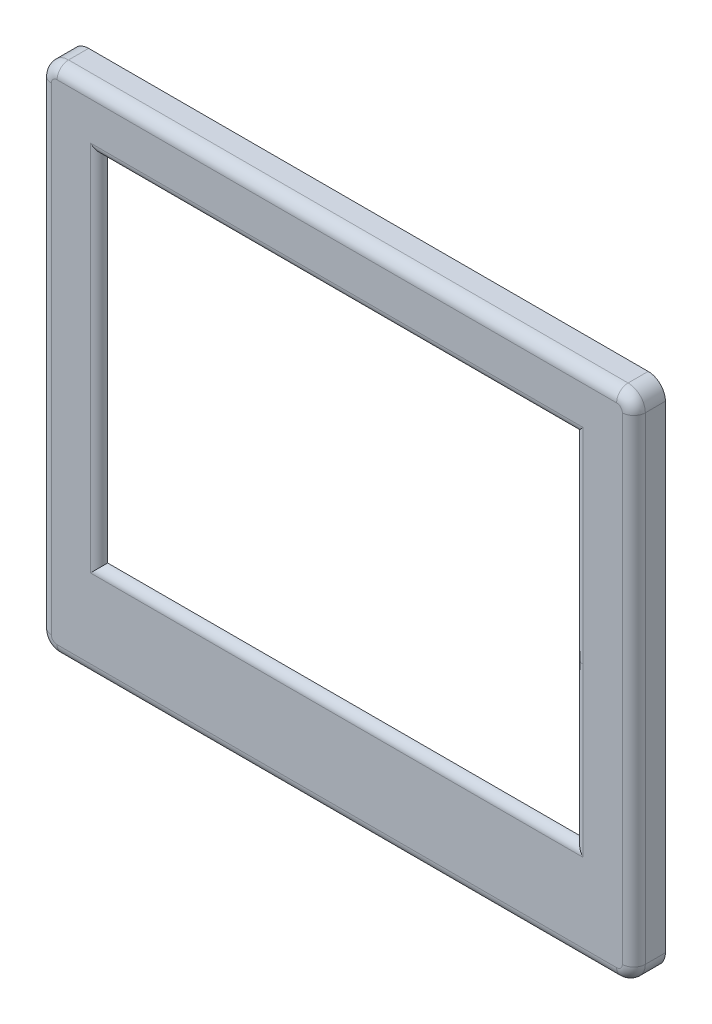
SolidWorks part; units mm, degrees
ref_plane "前视基准面" through (0, 0, 0) normal (0, 0, 1) x (1, 0, 0)
ref_plane "上视基准面" through (0, 0, 0) normal (0, 1, 0) x (1, 0, 0)
ref_plane "右视基准面" through (0, 0, 0) normal (1, 0, 0) x (0, 0, -1)
other "Configuration Table"
sketch "草图1" plane through (0, 0, 0) normal (0, 0, 1) x (1, 0, 0)
  line L0 (0, 0) -> (0, 44.3828) construction
  line L1 (-45.75, 38.75) -> (45.75, 38.75)
  line L2 (-45.75, 38.75) -> (-45.75, -38.75)
  line L3 (-45.75, -38.75) -> (45.75, -38.75)
  line L4 (45.75, 38.75) -> (45.75, -38.75)
  line L5 (-45.75, 38.75) -> (45.75, -38.75) construction
  line L6 (-45.75, -38.75) -> (45.75, 38.75) construction
  line L7 (-42.95, 35.75) -> (42.95, 35.75)
  line L8 (-42.95, 35.75) -> (-42.95, -29.15)
  line L9 (-42.95, -29.15) -> (42.95, -29.15)
  line L10 (42.95, 35.75) -> (42.95, -29.15)
  line L11 (-48.7681, 44.3828) -> (48.7681, 44.3828)
  line L12 (-51.7681, 41.3828) -> (-51.7681, -41.8828)
  line L13 (-48.7681, -44.8828) -> (48.7681, -44.8828)
  line L14 (51.7681, 41.3828) -> (51.7681, -41.8828)
  line L15 (0, 0) -> (-45.75, 0) construction
  line L16 (-8.75, -38.75) -> (-8.75, -41.25)
  line L17 (-8.75, -41.25) -> (8.75, -41.25)
  line L18 (8.75, -41.25) -> (8.75, -38.75)
  circle A0 centre (-48.2681, 40.8828) radius 1.65
  circle A1 centre (-48.2681, -40.8828) radius 1.65
  circle A2 centre (48.2681, -40.8828) radius 1.65
  circle A3 centre (48.2681, 40.8828) radius 1.65
  arc A4 (-51.7681, -41.8828) -> (-48.7681, -44.8828) centre (-48.7681, -41.8828) ccw
  arc A5 (51.7681, -41.8828) -> (48.7681, -44.8828) centre (48.7681, -41.8828) cw
  arc A6 (51.7681, 41.3828) -> (48.7681, 44.3828) centre (48.7681, 41.3828) ccw
  arc A7 (-48.7681, 44.3828) -> (-51.7681, 41.3828) centre (-48.7681, 41.3828) ccw
  point P0 (0, 0)
  point P6 (0, 0)
  dimension "D7" = 3.3
  dimension "D12" = 3.3
  dimension "D14" = 3
  dimension "D1" = 91.5
  dimension "D2" = 77.5
  dimension "D3" = 3
  dimension "D4" = 2.8
  dimension "D5" = 2.8
  dimension "D6" = 9.6
  dimension "D8" = 3.3
  dimension "D9" = 3.5
  dimension "D10" = 3.5
  dimension "D11" = 3.3
  dimension "D13" = 4
  dimension "D15" = 37
  dimension "D16" = 37
  dimension "D17" = 2.5
extrude "凸台-拉伸1" add sketch "草图1" against normal blind 4 contours L11 A7 L12 A4 L13 A5 L14 A6 A3 L1 L4 L3 L2 A0 A1 A2 region at (0, 43.0158, 0)
extrude "凸台-拉伸2" add sketch "草图1<3>" along normal blind 1.5 contours L11 A7 L12 A4 L13 A5 L14 A6 A3 L1 L4 L3 L2 A0 A1 A2 | A1 | A2 | A3 | A0 | L4 L1 L2 L3 L7 L10 L9 L8 | L17 L18 L3 L16 region at (0, 37.5509, 0) region at (0, -40, 0) region at (0, 43.0158, 0) region at (-48.2681, 40.8828, 0) region at (-48.2681, -40.8828, 0) region at (48.2681, -40.8828, 0) region at (48.2681, 40.8828, 0)
sketch "草图1<3>" plane through (0, 0, 0) normal (0, 0, 1) x (1, 0, 0) same geometry as "草图1"
fillet "圆角1" radius 2 8 edges at (-50.8895, -44.0042, 1.5) (-51.7681, -0.25, 1.5) (-50.8895, 43.5042, 1.5) (0, 44.3828, 1.5) (50.8895, 43.5042, 1.5) (51.7681, -0.25, 1.5) (50.8895, -44.0042, 1.5) (0, -44.8828, 1.5)
fillet "圆角2" radius 1 6 edges at (-45.75, 0, -4) (-27.25, -38.75, -4) (27.25, -38.75, -4) (0, 38.75, -4) (45.75, 0, -4) (0, -41.25, -4)
sketch "草图2" plane through (0, 0, -4) normal (0, 0, -1) x (-1, 0, 0)
  line L0 (0, 0) -> (0, -27.9281) construction
  line L1 (0, 0) -> (-18.0917, 0) construction
  line L2 (-47.75, 35) -> (-43.75, 35) construction
  line L4 (-45.75, 26.5) -> (-45.75, 23.5) construction
  line L5 (-45.75, 38.75) -> (-45.75, -38.75) construction
  line L6 (-46.0151, 36.8) -> (-45.4849, 36.8)
  line L7 (-46.0151, 33.2) -> (-45.4849, 33.2)
  line L8 (45.75, 26.5) -> (45.75, 23.5) construction
  line L9 (47.75, 35) -> (43.75, 35) construction
  line L10 (46.0151, 33.2) -> (45.4849, 33.2)
  line L11 (46.0151, 36.8) -> (45.4849, 36.8)
  line L12 (47.75, -35) -> (43.75, -35) construction
  line L13 (45.75, -26.5) -> (45.75, -23.5) construction
  line L14 (-45.75, -26.5) -> (-45.75, -23.5) construction
  line L15 (-47.75, -35) -> (-43.75, -35) construction
  line L16 (46.0151, -36.8) -> (45.4849, -36.8)
  line L17 (46.0151, -33.2) -> (45.4849, -33.2)
  line L18 (-46.0151, -33.2) -> (-45.4849, -33.2)
  line L19 (-46.0151, -36.8) -> (-45.4849, -36.8)
  arc A0 (-46.0151, 36.8) -> (-46.0151, 33.2) centre (-47.75, 35) ccw
  arc A1 (-45.4849, 33.2) -> (-45.4849, 36.8) centre (-43.75, 35) ccw
  arc A2 (45.4849, 33.2) -> (45.4849, 36.8) centre (43.75, 35) cw
  arc A3 (46.0151, 36.8) -> (46.0151, 33.2) centre (47.75, 35) cw
  arc A4 (46.0151, -36.8) -> (46.0151, -33.2) centre (47.75, -35) ccw
  arc A5 (45.4849, -33.2) -> (45.4849, -36.8) centre (43.75, -35) ccw
  arc A6 (-45.4849, -33.2) -> (-45.4849, -36.8) centre (-43.75, -35) cw
  arc A7 (-46.0151, -36.8) -> (-46.0151, -33.2) centre (-47.75, -35) cw
  dimension "D1" = 5
  dimension "D2" = 5
  dimension "D3" = 4
  dimension "D4" = 35
  dimension "D5" = 1.8
extrude "切除-拉伸1" cut sketch "草图2" against normal up to surface (4 mm away) up to face at (0, -20, 0)
sketch "草图3" plane through (0, 0, 0) normal (0, 0, -1) x (-1, 0, 0)
  line L0 (42.95, 35.75) -> (42.95, -29.15) construction
  line L1 (42.95, -29.15) -> (-42.95, -29.15) construction
  line L2 (-42.95, 35.75) -> (-42.95, -29.15) construction
  line L3 (42.95, 35.75) -> (-42.95, 35.75) construction
  line L4 (42.95, 35.75) -> (42.95, -29.15) construction
  line L5 (42.95, -29.15) -> (-42.95, -29.15) construction
  line L6 (-42.95, 35.75) -> (-42.95, -29.15) construction
  line L7 (42.95, 35.75) -> (-42.95, 35.75) construction
  line L8 (41.45, 34.25) -> (41.45, -27.65)
  line L9 (41.45, -27.65) -> (-41.45, -27.65)
  line L10 (-41.45, 34.25) -> (-41.45, -27.65)
  line L11 (41.45, 34.25) -> (-41.45, 34.25)
  dimension "D1" = 1.5
sketch "草图4" plane through (0, 0, 0) normal (0, 1, 0) x (1, 0, 0)
  line L0 (41.45, 0) -> (42.95, 0)
  line L1 (-41.45, 0) -> (41.45, 0) construction
  line L2 (-42.95, 0) -> (42.95, 0) construction
  line L3 (42.95, 0) -> (42.95, -1.5)
  arc A0 (41.45, 0) -> (42.95, -1.5) centre (42.95, 0) ccw
sweep "扫描1" add profiles "草图4" path "草图3"
sketch "草图5" plane through (0, 0, -4) normal (0, 0, -1) x (-1, 0, 0)
  line L0 (45.75, -33.2) -> (45.75, 33.2) construction
  line L1 (45.75, -33.2) -> (45.75, 33.2)
  line L13 (45.75, 9.3399) -> (49.25, 9.3399)
  line L14 (45.75, 9.3399) -> (45.75, 4.6872)
  line L15 (45.75, 4.6872) -> (49.25, 4.6872)
  line L16 (49.25, 9.3399) -> (49.25, 4.6872)
  line M21 (46.75, 32.7087) -> (46.75, -32.7087)
  dimension "D1" = 3.5
extrude "切除-拉伸2" cut sketch "草图5" against normal blind 1 contours L16 L13 L15 M21 | L1 L15 L13 M21 region at (-46.25, 7.0135, -4) region at (-48, 7.0135, -4)
